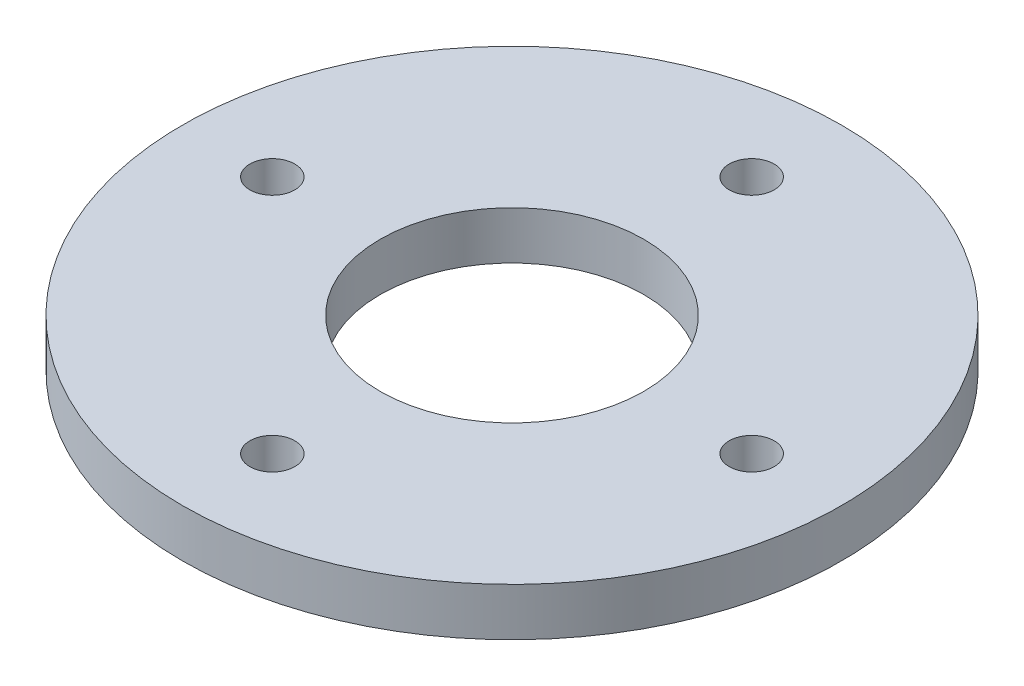
SolidWorks part; units mm, degrees
ref_plane "Front Plane" through (0, 0, 0) normal (0, 0, 1) x (1, 0, 0)
ref_plane "Top Plane" through (0, 0, 0) normal (0, 1, 0) x (1, 0, 0)
ref_plane "Right Plane" through (0, 0, 0) normal (1, 0, 0) x (0, 0, -1)
sketch "Sketch1" plane through (0, 0, 0) normal (0, 1, 0) x (1, 0, 0)
  circle A0 centre (0, 0) radius 27.5
  circle A2 centre (0, 20) radius 2.5
  circle A3 centre (-20, 0) radius 2.5
  circle A4 centre (20, 0) radius 2.5
  circle A5 centre (0, -20) radius 2.5
extrude "Boss-Extrude1" add sketch "Sketch1" along normal blind 4
sketch "Sketch2" plane through (0, 4, 0) normal (0, 1, 0) x (1, 0, 0)
  circle A0 centre (0, 0) radius 11
extrude "Cut-Extrude1" cut sketch "Sketch2" against normal blind 15
sketch "Sketch3" plane through (0, 4, 0) normal (0, 1, 0) x (1, 0, 0)
  circle A0 centre (0, -20) radius 2.5 construction
  circle A1 centre (20, 0) radius 2.5 construction
  circle A2 centre (0, 20) radius 2.5 construction
  circle A3 centre (-20, 0) radius 2.5 construction
  circle A4 centre (0, -20) radius 2.5
  circle A5 centre (20, 0) radius 2.5
  circle A6 centre (0, 20) radius 2.5
  circle A7 centre (-20, 0) radius 2.5
  circle A8 centre (-20, 0) radius 1.875
  circle A9 centre (0, 20) radius 1.875
  circle A10 centre (20, 0) radius 1.875
  circle A11 centre (0, -20) radius 1.875
extrude "Boss-Extrude3" add sketch "Sketch3" against normal up to surface (4 mm away) up to face at (0, 0, 11)
